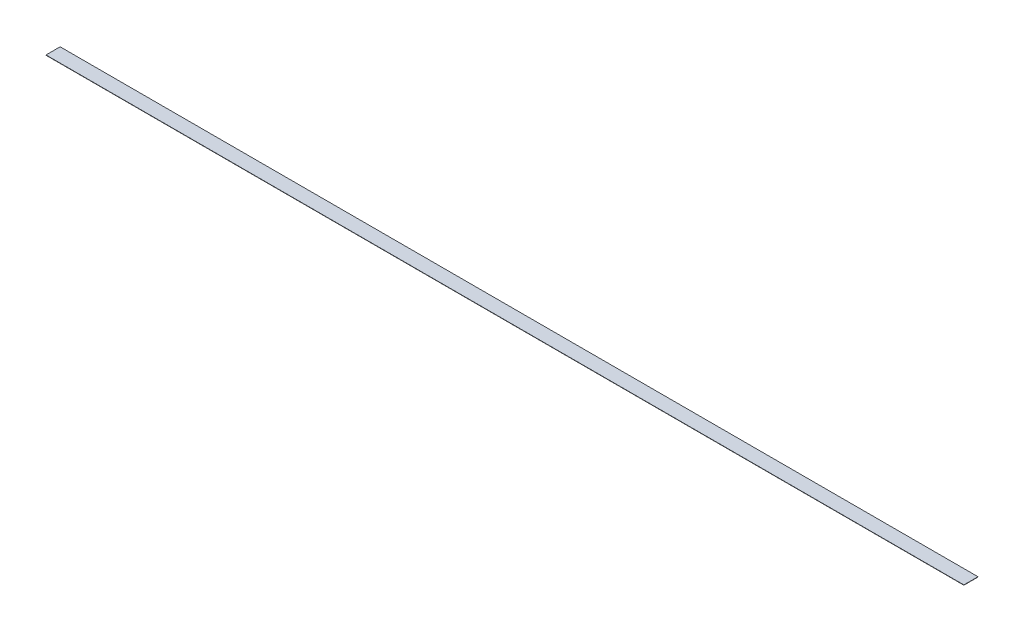
SolidWorks part; units mm, degrees
material "Acrylic (Medium-high impact)"
ref_plane "Front Plane" through (0, 0, 0) normal (0, 0, 1) x (1, 0, 0)
ref_plane "Top Plane" through (0, 0, 0) normal (0, 1, 0) x (1, 0, 0)
ref_plane "Right Plane" through (0, 0, 0) normal (1, 0, 0) x (0, 0, -1)
sketch "Sketch1" plane through (0, 0, 0) normal (0, 0, 1) x (1, 0, 0)
  line L0 (0, 0.0635) -> (206.375, 0) construction
  line L1 (0, 0) -> (206.375, 0) construction
  line L2 (0, 0) -> (0, 0.0635) construction
  line L3 (0, 0.0635) -> (206.375, 0.0635) construction
  line L4 (206.375, 0) -> (206.375, 0.0635) construction
  line L6 (0.0635, 0.0635) -> (206.3115, 0.0635)
  line L7 (0.0635, 0.0635) -> (0.0635, 0)
  line L8 (0.0635, 0) -> (206.3115, 0)
  line L9 (206.3115, 0.0635) -> (206.3115, 0)
  line L10 (0.0635, 0.0635) -> (206.3115, 0) construction
  line L11 (0.0635, 0) -> (206.3115, 0.0635) construction
  point P5 (103.1875, 0.0317)
  dimension "D1" = 0.0635
  dimension "D2" = 206.375
  dimension "D3" = 0.127
  dimension "D4" = 0.0635
extrude "Boss-Extrude1" add sketch "Sketch1" along normal blind 3.175
fillet "Fillet1" radius 0.7937 rebuild error yes
sketch "Sketch2" plane through (0, 0, 3.175) normal (0, 0, 1) x (1, 0, 0)
  line L0 (205.0415, 0) -> (205.0415, -1.2065) construction
  line L3 (206.3115, 0) -> (206.3115, 0.0635) construction
  line L4 (0.0635, 0) -> (206.3115, 0) construction
  line L5 (206.3115, 0.0635) -> (0.0635, 0.0635) construction
  text T0 "window_5/1000\"" font "Consolas" height 3.5
  dimension "D1" = 1.27
  dimension "D2" = 1.27
extrude "Cut-Extrude1" [suppressed] cut sketch "Sketch2" against normal blind 1.27
